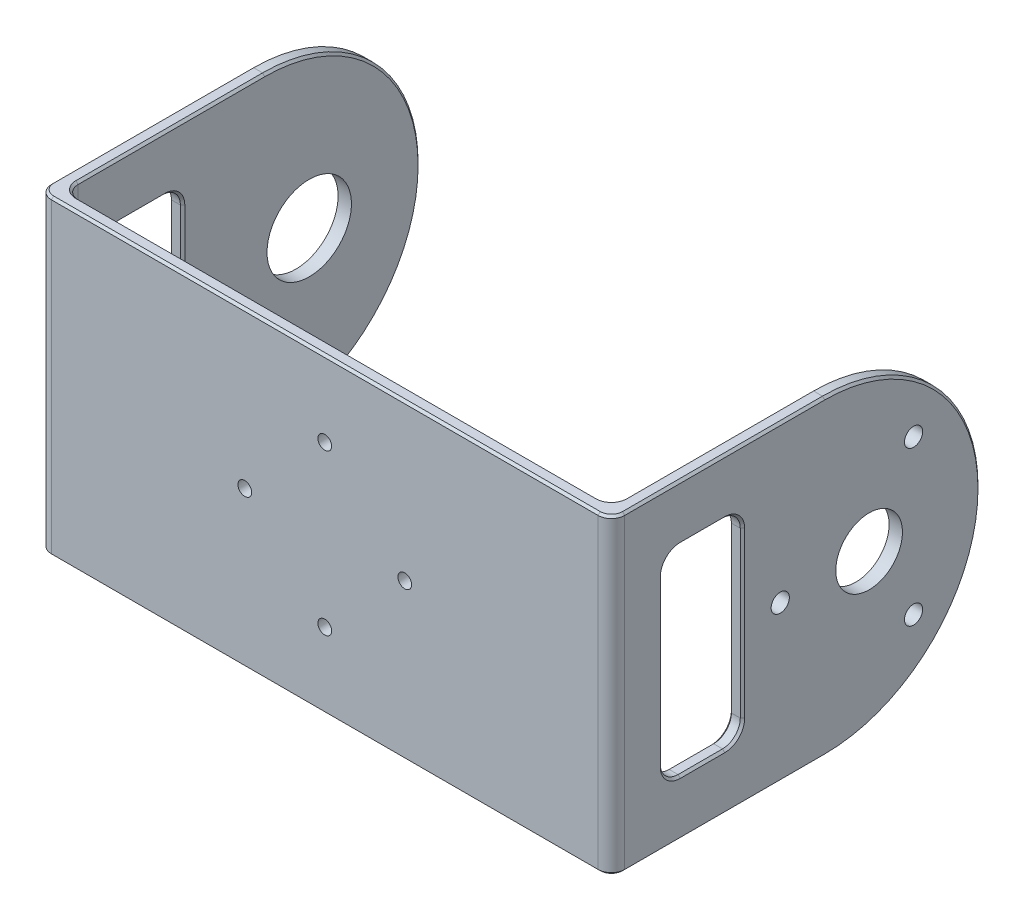
SolidWorks part; units mm, degrees
material "6061 合金"
ref_plane "前视基准面" through (0, 0, 0) normal (0, 0, 1) x (1, 0, 0)
ref_plane "上视基准面" through (0, 0, 0) normal (0, 1, 0) x (1, 0, 0)
ref_plane "右视基准面" through (0, 0, 0) normal (1, 0, 0) x (0, 0, -1)
sketch "草图1" plane through (0, 0, 0) normal (0, 1, 0) x (1, 0, 0)
  line L0 (-64.5, 0) -> (64.5, 0)
  line L1 (0, 0) -> (0, 3) construction
  line L2 (-61.5, 3) -> (61.5, 3)
  line L3 (-61.5, 3) -> (-61.5, 83)
  line L4 (-64.5, 0) -> (-64.5, 83)
  line L5 (-64.5, 83) -> (-61.5, 83)
  line L6 (64.5, 83) -> (61.5, 83)
  line L7 (64.5, 0) -> (64.5, 83)
  line L8 (61.5, 3) -> (61.5, 83)
extrude "宽70mm" add sketch "草图1" along normal blind 70
fillet "圆角1" radius 3 4 edges at (64.5, 35, 0) (-64.5, 35, 0) (-61.5, 35, -3) (61.5, 35, -3)
sketch "草图2" plane through (64.5, 0, 0) normal (1, 0, 0) x (0, 0, -1)
  line L0 (83, 70) -> (83, 0) construction
  circle A0 centre (58, 35) radius 20 construction
  circle A1 centre (38, 35) radius 2.05
  circle A2 centre (68, 52.3205) radius 2.05
  circle A3 centre (68, 17.6795) radius 2.05
  circle A4 centre (58, 35) radius 7.5
  point P2 (83, 35)
  point P14 (58, 35)
  dimension "D2" = 40
  dimension "D3" = 4.1
  dimension "D5" = 15
  dimension "D1" = 25
  dimension "D4" = 3
extrude "切除-拉伸1" cut sketch "草图2" against normal up to next
sketch "草图3" plane through (-64.5, 0, 0) normal (-1, 0, 0) x (0, 0, 1)
  line L0 (-83, 70) -> (-83, 0) construction
  circle A0 centre (-58, 35) radius 9.5
  dimension "D1" = 19
  dimension "D2" = 25
extrude "切除-拉伸2" cut sketch "草图3" against normal up to next
sketch "草图4" plane through (64.5, 0, 0) normal (1, 0, 0) x (0, 0, -1)
  line L0 (0, 0) -> (0, 70) construction
  line L1 (11.5, 57.5) -> (29.5, 57.5)
  line L2 (11.5, 57.5) -> (11.5, 12.5)
  line L3 (11.5, 12.5) -> (29.5, 12.5)
  line L4 (29.5, 57.5) -> (29.5, 12.5)
  line L5 (11.5, 57.5) -> (29.5, 12.5) construction
  line L6 (11.5, 12.5) -> (29.5, 57.5) construction
  point P0 (20.5, 35)
  dimension "D1" = 20.5
  dimension "D2" = 18
  dimension "D3" = 45
extrude "切除-拉伸3" cut sketch "草图4" against normal through all
fillet "圆角2" radius 4 8 edges at (-63, 57.5, -29.5) (-63, 57.5, -11.5) (-63, 12.5, -29.5) (-63, 12.5, -11.5) (63, 12.5, -29.5) (63, 57.5, -29.5) (63, 12.5, -11.5) (63, 57.5, -11.5)
fillet "圆角3" radius 35 4 edges at (63, 70, -83) (-63, 70, -83) (-63, 0, -83) (63, 0, -83)
sketch "草图5" plane through (0, 0, -3) normal (0, 0, -1) x (-1, 0, 0)
  circle A0 centre (0, 53) radius 1.5
  circle A1 centre (18, 35) radius 1.5
  circle A2 centre (0, 17) radius 1.5
  circle A3 centre (-18, 35) radius 1.5
  circle A4 centre (0, 35) radius 18 construction
  point P12 (0, 35)
  point P13 (0, 36)
  point P19 (0, 35)
  dimension "D1" = 36
  dimension "D2" = 3
  dimension "D3" = 4
hole_wizard "Ø3.1 (3.1) 直径孔1" positions "3D草图3" profile "草图8" hole size "Ø3.1" standard "GB" end condition up to next
sketch3d "3D草图3"
  point P0 (0, 53, -3)
  point P3 (18, 35, -3)
  point P6 (0, 17, -3)
  point P9 (-18, 35, -3)
sketch "草图8" plane through (0, 53, -3) normal (1, 0, 0) x (0, 1, 0)
  line L0 (0, 0) -> (0, 3)
  line L1 (0, 3) -> (1.55, 3)
  line L2 (1.55, 3) -> (1.55, 0)
  line L5 (1.55, 0) -> (0, 0)
  line L11 (0, -6.35) -> (0, 107.95) construction
  dimension "通孔孔直径" = 3.1
  dimension "通孔孔深度" = 3
chamfer "倒角1" distance 0.5 angle 45 60 edges at (0, 70, 0) (-63.6213, 70, -0.8787) (63.6213, 70, -0.8787) (-64.5, 70, -25.5) (64.5, 70, -25.5) (-64.5, 59.7487, -72.7487) (64.5, 59.7487, -72.7487) (-64.5, 10.2513, -72.7487) (64.5, 10.2513, -72.7487) (-64.5, 0, -25.5) (64.5, 0, -25.5) (-63.6213, 0, -0.8787) (63.6213, 0, -0.8787) (0, 0, 0) (0, 70, -3) (60.6213, 70, -3.8787) (-60.6213, 70, -3.8787) (61.5, 70, -27) (-61.5, 70, -27) (61.5, 59.7487, -72.7487) (-61.5, 59.7487, -72.7487) (61.5, 10.2513, -72.7487) (-61.5, 10.2513, -72.7487) (61.5, 0, -27) (-61.5, 0, -27) (60.6213, 0, -3.8787) (-60.6213, 0, -3.8787) (0, 0, -3) (-61.5, 12.5, -20.5) (-61.5, 13.6716, -12.6716) (-61.5, 13.6716, -28.3284) (-61.5, 35, -11.5) (-61.5, 35, -29.5) (-61.5, 56.3284, -12.6716) (-61.5, 56.3284, -28.3284) (-61.5, 57.5, -20.5) (-64.5, 12.5, -20.5) (-64.5, 13.6716, -28.3284) (-64.5, 13.6716, -12.6716) (-64.5, 35, -29.5) (-64.5, 35, -11.5) (-64.5, 56.3284, -28.3284) (-64.5, 56.3284, -12.6716) (-64.5, 57.5, -20.5) (61.5, 35, -29.5) (61.5, 56.3284, -28.3284) (61.5, 13.6716, -28.3284) (61.5, 57.5, -20.5) (61.5, 12.5, -20.5) (61.5, 56.3284, -12.6716) (61.5, 13.6716, -12.6716) (61.5, 35, -11.5) (64.5, 12.5, -20.5) (64.5, 13.6716, -28.3284) (64.5, 13.6716, -12.6716) (64.5, 35, -29.5) (64.5, 35, -11.5) (64.5, 56.3284, -28.3284) (64.5, 56.3284, -12.6716) (64.5, 57.5, -20.5)
